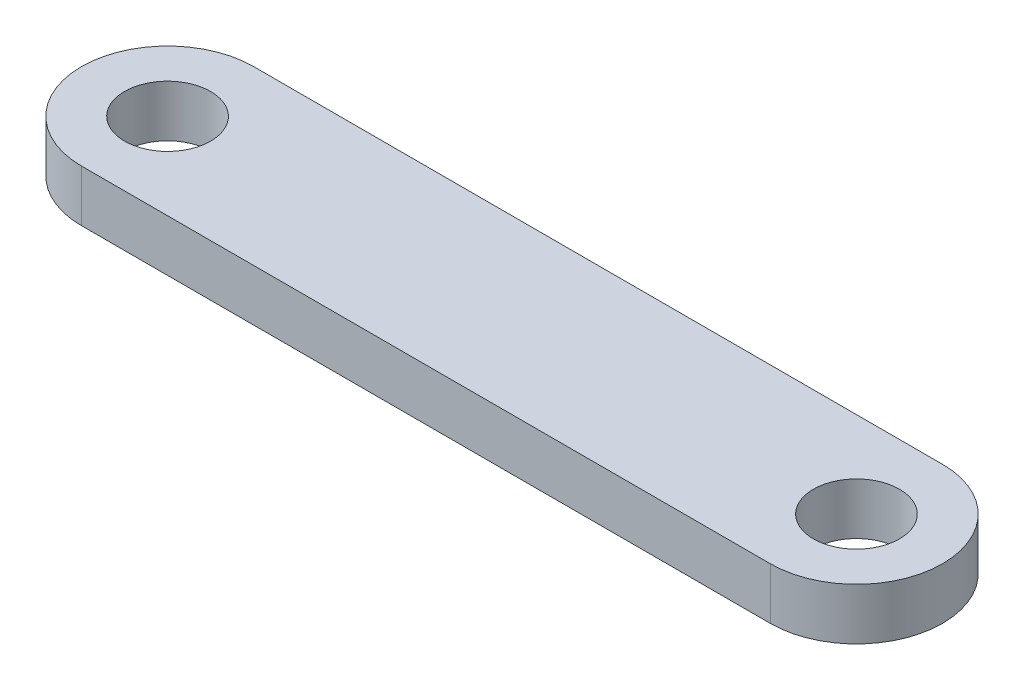
SolidWorks part; units mm, degrees
ref_plane "Front Plane" through (0, 0, 0) normal (0, 0, 1) x (1, 0, 0)
ref_plane "Top Plane" through (0, 0, 0) normal (0, 1, 0) x (1, 0, 0)
ref_plane "Right Plane" through (0, 0, 0) normal (1, 0, 0) x (0, 0, -1)
sketch "Sketch1" plane through (0, 0, 0) normal (0, 1, 0) x (1, 0, 0)
  line L0 (-25.4, 0) -> (25.4, 0) construction
  line L1 (-25.4, 6.35) -> (25.4, 6.35)
  line L2 (-25.4, -6.35) -> (25.4, -6.35)
  arc A0 (-25.4, 6.35) -> (-25.4, -6.35) centre (-25.4, 0) ccw
  arc A1 (25.4, -6.35) -> (25.4, 6.35) centre (25.4, 0) ccw
  circle A2 centre (-25.4, 0) radius 3.175
  circle A3 centre (25.4, 0) radius 3.175
  point P3 (0, 0)
  dimension "D2" = 6.35
  dimension "D3" = 6.35
  dimension "D4" = 6.35
  dimension "D1" = 50.8
extrude "Boss-Extrude1" add sketch "Sketch1" along normal blind 3.81
